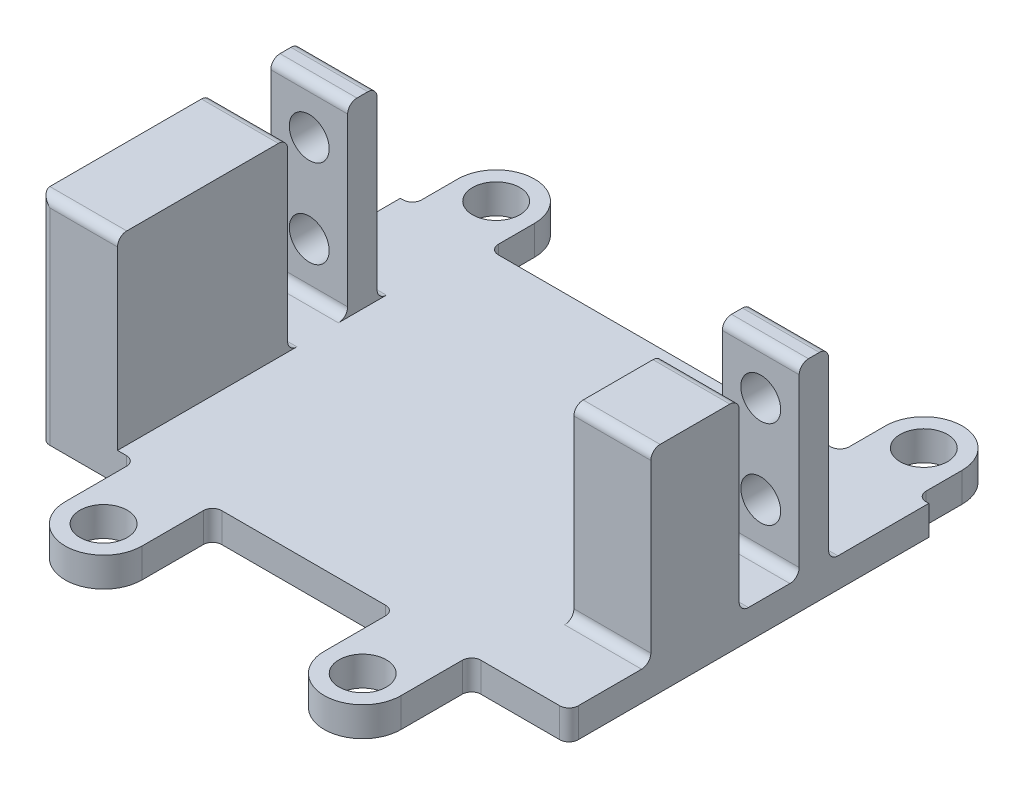
SolidWorks part; units mm, degrees
ref_plane "Front Plane" through (0, 0, 0) normal (0, 0, 1) x (1, 0, 0)
ref_plane "Top Plane" through (0, 0, 0) normal (0, 1, 0) x (1, 0, 0)
ref_plane "Right Plane" through (0, 0, 0) normal (1, 0, 0) x (0, 0, -1)
sketch "Sketch1" plane through (0, 0, 0) normal (0, 1, 0) x (1, 0, 0)
  line L1 (0, 0) -> (54.4, 0)
  line L2 (0, 0) -> (0, 38.8)
  line L3 (0, 38.8) -> (54.4, 38.8)
  line L4 (54.4, 0) -> (54.4, 38.8)
  dimension "D1" = 54.4
  dimension "D2" = 38.8
extrude "Boss-Extrude1" add sketch "Sketch1" along normal blind 3.175
sketch "Sketch2" plane through (0, 3.175, 0) normal (0, 1, 0) x (1, 0, 0)
  line L0 (0, 38.8) -> (0, 0) construction
  line L1 (0, 28) -> (7, 28)
  line L2 (0, 28) -> (0, 24.825)
  line L3 (0, 24.825) -> (7, 24.825)
  line L4 (7, 28) -> (7, 24.825)
  line L5 (54.4, 38.8) -> (0, 38.8) construction
  dimension "D1" = 3.175
  dimension "D2" = 10.8
  dimension "D3" = 7
extrude "Boss-Extrude2" add sketch "Sketch2" along normal blind 20
ref_plane "Plane1" through (27.2, 0, 0) normal (-1, 0, 0) x (0, 0, 1)
mirror "Mirror1" about plane through (27.2, 0, 0) normal (-1, 0, 0) of "Boss-Extrude2"
sketch "Sketch3" plane through (0, 3.175, 0) normal (0, 1, 0) x (1, 0, 0)
  line L0 (8.9698, -7.608) -> (8.9698, 0)
  line L1 (0, 0) -> (54.4, 0) construction
  line L2 (17.2502, -7.608) -> (17.2502, 0)
  circle A0 centre (13.11, -7.608) radius 2.5527
  circle A2 centre (13.11, -7.608) radius 4.1402
  line M12 (0, 0) -> (54.4, 0)
  dimension "D1" = 5.1054
  dimension "D4" = 1.5875
  dimension "D2" = 7.608
  dimension "D3" = 13.11
extrude "Boss-Extrude3" add sketch "Sketch3" against normal up to surface (3.175 mm away) contours A2 A0 | A2 L2 L0 M12 region at (13.11, 3.175, 2.2762) region at (13.11, 3.175, 3.5849) up to face at (27.2, 0, -19.4)
pattern_linear "LPattern1" count 2 spacing 27.94 along (1, 0, 0) of "Boss-Extrude3"
sketch "Sketch4" plane through (0, 3.175, 0) normal (0, 1, 0) x (1, 0, 0)
  line L0 (54.4, 0) -> (54.4, 24.825) construction
  line L1 (54.4, 18.35) -> (47.4, 18.35)
  line L2 (54.4, 18.35) -> (54.4, 8.825)
  line L3 (54.4, 8.825) -> (47.4, 8.825)
  line L4 (47.4, 18.35) -> (47.4, 8.825)
  line L5 (54.4, 24.825) -> (47.4, 24.825) construction
  dimension "D1" = 16
  dimension "D2" = 9.525
extrude "Boss-Extrude4" add sketch "Sketch4" along normal up to surface (20 mm away) up to face at (50.9, 23.175, -26.4125)
mirror "Mirror2" about plane through (27.2, 0, 0) normal (-1, 0, 0) of "Boss-Extrude4"
sketch "Sketch5" plane through (0, 0, 0) normal (-1, 0, 0) x (0, 0, 1)
  line L1 (-8.825, 23.175) -> (0, 23.175)
  line L2 (-8.825, 23.175) -> (-8.825, 3.175)
  line L3 (-8.825, 3.175) -> (0, 3.175)
  line L4 (0, 23.175) -> (0, 3.175)
extrude "Boss-Extrude5" add sketch "Sketch5" against normal up to surface (7 mm away) up to face at (7, 13.175, -13.5875)
sketch "Sketch6" plane through (0, 3.175, 0) normal (0, 1, 0) x (1, 0, 0)
  line L0 (0, 38.8) -> (0, 28) construction
  line L1 (0, 43.7) -> (0, 38.8)
  line L2 (8.2804, 43.7) -> (8.2804, 38.8)
  line L3 (54.4, 38.8) -> (0, 38.8) construction
  circle A0 centre (4.1402, 43.7) radius 2.5527
  circle A1 centre (13.11, -7.608) radius 2.5527 construction
  circle A2 centre (4.1402, 43.7) radius 4.1402
  line M24 (54.4, 38.8) -> (0, 38.8)
  dimension "D2" = 5.1054
  dimension "D4" = 1.5875
  dimension "D1" = 51.308
  dimension "D3" = 4.1402
extrude "Boss-Extrude6" add sketch "Sketch6" against normal up to surface (3.175 mm away) contours A2 A0 | A2 L1 L2 M24 region at (4.1402, 3.175, -39.4636) region at (4.1402, 3.175, -47.7231) up to face at (27.12, 0, -3.2406)
mirror "Mirror3" about plane through (27.2, 0, 0) normal (-1, 0, 0) of "Boss-Extrude6"
sketch "Sketch7" plane through (0, 0, -28) normal (0, 0, -1) x (-1, 0, 0)
  line L0 (-7, 23.175) -> (-7, 3.175) construction
  line L1 (-7, 23.175) -> (0, 23.175) construction
  circle A0 centre (-2.8526, 17.925) radius 2.15
  circle A1 centre (-2.8526, 8.425) radius 2.15
  point P4 (0, 0)
  dimension "D1" = 4.3
  dimension "D2" = 4.1474
  dimension "D3" = 5.25
  dimension "D4" = 9.5
extrude "Cut-Extrude1" cut sketch "Sketch7" against normal up to surface (3.175 mm away) up to face at (3.5, 13.175, -24.825)
sketch "Sketch9" plane through (0, 0, 0) normal (-1, 0, 0) x (0, 0, 1)
  line L0 (-38.8, 0) -> (-38.8, 3.175) construction
  line L1 (-38.8, 0) -> (-38.8, 3.175)
  line L2 (-38.8, 3.175) -> (-28, 3.175)
  line L3 (-28, 3.175) -> (-28, 23.175)
  line L4 (-28, 23.175) -> (-24.825, 23.175)
  line L5 (-24.825, 23.175) -> (-24.825, 3.175)
  line L6 (-24.825, 3.175) -> (-18.35, 3.175)
  line L7 (-18.35, 3.175) -> (-18.35, 23.175)
  line L8 (-18.35, 23.175) -> (0, 23.175)
  line L9 (0, 23.175) -> (0, 0)
  line L10 (0, 0) -> (-38.8, 0)
extrude "Boss-Extrude7" add sketch "Sketch9" along normal blind 1.2948
mirror "Mirror4" about plane through (27.2, 0, 0) normal (-1, 0, 0) of "Boss-Extrude7"
sketch "Sketch10" plane through (54.4, 0, 0) normal (-1, 0, 0) x (0, 0, 1)
  line L1 (-8.825, 23.175) -> (0, 23.175)
  line L2 (-8.825, 23.175) -> (-8.825, 3.175)
  line L3 (-8.825, 3.175) -> (0, 3.175)
  line L4 (0, 23.175) -> (0, 3.175)
extrude "Cut-Extrude3" cut sketch "Sketch10" against normal up to surface (1.2948 mm away) up to face at (55.6948, 10.54, -21.995)
mirror "Mirror5" about plane through (27.2, 0, 0) normal (-1, 0, 0) of "Cut-Extrude1"
fillet "Fillet1" radius 1 25 edges at (51.5474, 23.175, -18.35) (51.5474, 23.175, -8.825) (51.5474, 3.175, -8.825) (51.5474, 3.175, -24.825) (51.5474, 3.175, -28) (51.5474, 3.175, -18.35) (-1.2948, 11.5875, 0) (55.6948, 1.5875, 0) (45.1902, 1.5875, 0) (36.9098, 1.5875, 0) (8.9698, 1.5875, 0) (17.2502, 1.5875, 0) (2.8526, 23.175, 0) (2.8526, 23.175, -18.35) (2.8526, 3.175, -18.35) (2.8526, 3.175, -24.825) (2.8526, 3.175, -28) (2.8526, 23.175, -28) (2.8526, 23.175, -24.825) (0, 1.5875, -38.8) (8.2804, 1.5875, -38.8) (46.1196, 1.5875, -38.8) (54.4, 1.5875, -38.8) (51.5474, 23.175, -24.825) (51.5474, 23.175, -28)
